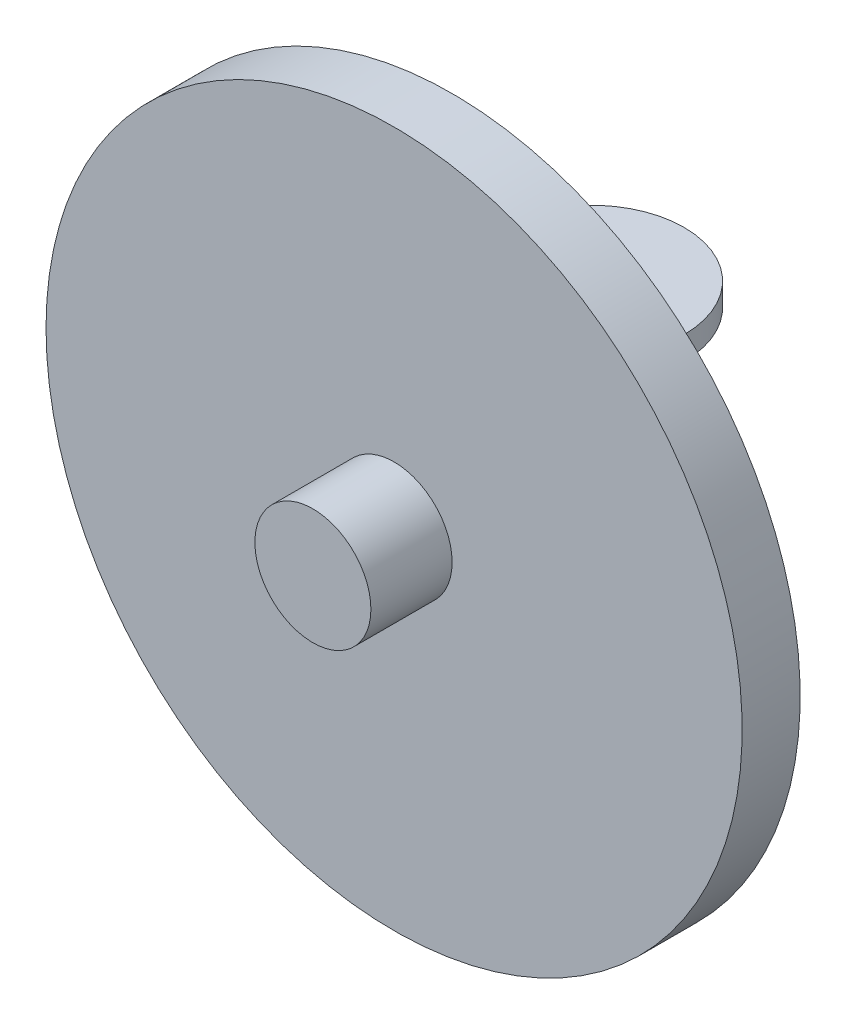
SolidWorks part; units mm, degrees
ref_plane "Front Plane" through (0, 0, 0) normal (0, 0, 1) x (1, 0, 0)
ref_plane "Top Plane" through (0, 0, 0) normal (0, 1, 0) x (1, 0, 0)
ref_plane "Right Plane" through (0, 0, 0) normal (1, 0, 0) x (0, 0, -1)
sketch "Sketch2" plane through (0, 0, 0) normal (0, 0, 1) x (1, 0, 0)
  circle A0 centre (0, 0) radius 25
  dimension "D1" = 50
extrude "Boss-Extrude1" add sketch "Sketch2" along normal blind 35
sketch "Sketch3" plane through (0, 0, 0) normal (0, 0, -1) x (-1, 0, 0)
  circle A0 centre (0, 0) radius 150
  dimension "D1" = 300
extrude "Boss-Extrude2" add sketch "Sketch3" along normal blind 25
sketch "Sketch4" plane through (0, 0, -25) normal (0, 0, -1) x (-1, 0, 0)
  line L1 (40, 50) -> (-40, 50)
  line L2 (40, 50) -> (40, -50)
  line L3 (40, -50) -> (-40, -50)
  line L4 (-40, 50) -> (-40, -50)
  line L5 (40, 50) -> (-40, -50) construction
  line L6 (40, -50) -> (-40, 50) construction
  line L7 (40, -40) -> (-40, -40)
  line L8 (40, -40) -> (40, 40)
  line L9 (40, 40) -> (-40, 40)
  line L10 (-40, -40) -> (-40, 40)
  line L11 (40, -40) -> (-40, 40) construction
  line L12 (40, 40) -> (-40, -40) construction
  point P0 (0, 0)
  point P6 (0, 0)
  dimension "D1" = 80
  dimension "D2" = 100
  dimension "D3" = 80
extrude "Boss-Extrude3" add sketch "Sketch4" along normal blind 100 contours L9 L2 L1 L4 | L2 L7 L4 L3 region at (0, 45, -25) region at (0, -45, -25)
sketch "Sketch5" plane through (0, -50, 0) normal (0, -1, 0) x (1, 0, 0)
  line L0 (0, -25) -> (0, -125) construction
  line L1 (-40, -25) -> (40, -25) construction
  line L2 (-40, -125) -> (40, -125) construction
  circle A0 centre (0, -75) radius 25
  dimension "D1" = 50
extrude "Cut-Extrude1" cut sketch "Sketch5" against normal blind 100
fillet "Fillet1" radius 40 4 edges at (-40, 45, -125) (40, 45, -125) (40, -45, -125) (-40, -45, -125)
